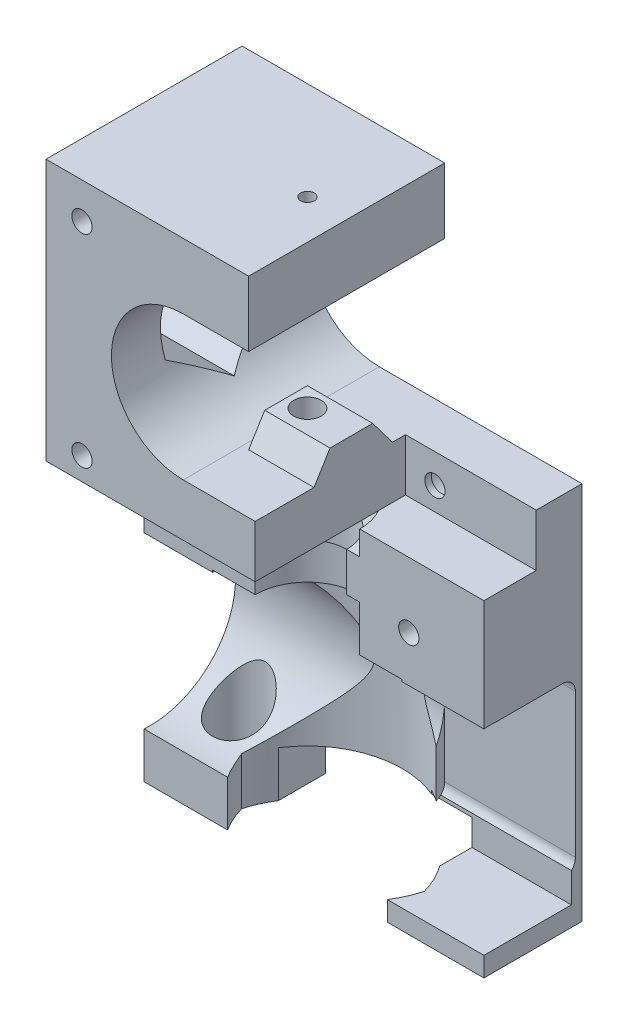
SolidWorks part; units mm, degrees
note: The reader was unsure of these and kept them because the rebuilt part matched: shared geometry of "Croquis16<3>".
ref_plane "Alzado" through (0, 0, 0) normal (0, 0, 1) x (1, 0, 0)
ref_plane "Planta" through (0, 0, 0) normal (0, 1, 0) x (1, 0, 0)
ref_plane "Vista lateral" through (0, 0, 0) normal (1, 0, 0) x (0, 0, -1)
sketch "Croquis2" plane through (0, 0, 0) normal (0, 0, 1) x (1, 0, 0)
  line L0 (0, 0) -> (0, 90)
  line L1 (0, 90) -> (21, 90)
  line L2 (27, 80) -> (31, 80)
  line L3 (21, 58) -> (42, 58)
  line L4 (42, 58) -> (42, 0)
  line L5 (42, 0) -> (0, 0)
  line L6 (21, 80) -> (27, 80)
  line L7 (21, 90) -> (27, 90)
  line L9 (31, 80) -> (31, 90)
  line L10 (31, 90) -> (27, 90)
  circle A0 centre (5.5, 84.5) radius 1.55
  circle A1 centre (5.5, 53.5) radius 1.55
  circle A2 centre (36.5, 53.5) radius 1.55
  arc A3 (21, 80) -> (21, 58) centre (21, 69) ccw
  dimension "D5" = 3.1
  dimension "D6" = 3.1
  dimension "D7" = 3.1
  dimension "D12" = 22
  dimension "D1" = 90
  dimension "D2" = 42
  dimension "D3" = 6
  dimension "D4" = 10
  dimension "D8" = 5.5
  dimension "D9" = 31
  dimension "D10" = 31
  dimension "D11" = 27
  dimension "D13" = 15.5
  dimension "D14" = 15.5
  dimension "D15" = 4
  dimension "D16" = 10
  dimension "D17" = 21
extrude "Saliente-Extruir1" add sketch "Croquis2" along normal blind 30
sketch "Croquis3" plane through (0, 0, 0) normal (0, 0, -1) x (-1, 0, 0)
  circle A0 centre (-5.5, 84.5) radius 1.55 construction
  circle A1 centre (-5.5, 53.5) radius 1.55 construction
  circle A2 centre (-36.5, 53.5) radius 1.55 construction
  circle A3 centre (-5.5, 84.5) radius 1.55
  circle A4 centre (-5.5, 53.5) radius 1.55
  circle A5 centre (-36.5, 53.5) radius 1.55
  circle A6 centre (-36.5, 53.5) radius 2.8
  circle A7 centre (-5.5, 53.5) radius 2.8
  circle A8 centre (-5.5, 84.5) radius 2.8
  dimension "D1" = 5.6
  dimension "D2" = 5.6
  dimension "D3" = 5.6
extrude "Cortar-Extruir1" cut sketch "Croquis3" against normal blind 6
sketch "Croquis5" plane through (0, 0, 30) normal (0, 0, 1) x (1, 0, 0)
  line L0 (32, 58) -> (32, 50)
  line L1 (42, 58) -> (21, 58) construction
  line L2 (32, 50) -> (42, 50)
  line L3 (42, 0) -> (42, 58) construction
  line L4 (42, 0) -> (42, 58)
  line L5 (42, 58) -> (32, 58)
  line M7 (42, 0) -> (42, 58)
  line M8 (42, 58) -> (21, 58)
  circle M15 centre (36.5, 53.5) radius 1.55
  dimension "D1" = 10
  dimension "D2" = 8
extrude "Cortar-Extruir2" cut sketch "Croquis5" against normal blind 23 contours L0 L2 M7 M8 M15
sketch "Croquis6" plane through (0, 0, 30) normal (0, 0, 1) x (1, 0, 0)
  line L0 (42, 50) -> (0, 50)
  line L1 (0, 90) -> (0, 0) construction
  line L2 (0, 50) -> (0, 0)
  line L3 (0, 0) -> (42, 0)
  line L4 (42, 0) -> (42, 50)
extrude "Cortar-Extruir3" cut sketch "Croquis6" against normal blind 15
sketch "Croquis8" plane through (0, 90, 0) normal (0, 1, 0) x (1, 0, 0)
  line L0 (31, 0) -> (0, 0) construction
  line L1 (31, -30) -> (31, 0) construction
  circle A0 centre (25, -15) radius 1.05
  dimension "D1" = 2.1
  dimension "D2" = 15
  dimension "D3" = 6
extrude "Cortar-Extruir4" cut sketch "Croquis8" against normal up to surface (40 mm away) up to face at (16, 50, 22.5)
sketch "Croquis9" plane through (0, 0, 0) normal (-1, 0, 0) x (0, 0, 1)
  line L0 (0, 90) -> (0, 0) construction
  line L1 (15, 60.6795) -> (22.5, 65.0096)
  line L2 (22.5, 65.0096) -> (22.5, 73.6699)
  line L3 (22.5, 73.6699) -> (15, 78)
  line L4 (15, 78) -> (7.5, 73.6699)
  line L5 (7.5, 73.6699) -> (7.5, 65.0096)
  line L6 (7.5, 65.0096) -> (15, 60.6795)
  circle A0 centre (15, 69.3397) radius 7.5 construction
  dimension "D3" = 15
  dimension "D1" = 15
  dimension "D2" = 12
extrude "Cortar-Extruir5" cut sketch "Croquis9" against normal up to surface (11.0405 mm away)
sketch "Croquis13" plane through (0, 0, 15) normal (0, 0, 1) x (1, 0, 0)
  line L0 (26.05, 50) -> (23.95, 50) construction
  line L1 (26.05, 50) -> (23.95, 50) construction
  line L2 (25, 50) -> (17, 50)
  line L3 (32, 50) -> (0, 50) construction
  line L4 (17, 50) -> (17, 46.3)
  line L5 (17, 46.3) -> (19, 46.3)
  line L6 (19, 46.3) -> (19, 40.3)
  line L7 (19, 40.3) -> (17, 40.3)
  line L8 (17, 40.3) -> (17, 33.3)
  line L15 (17, 33.3) -> (10.5, 33.3)
  line L16 (25, 50) -> (25, 7.3)
  line L17 (10.5, 33.3) -> (10.5, 7.3)
  line L18 (10.5, 7.3) -> (25, 7.3)
  dimension "D1" = 8
  dimension "D2" = 3.7
  dimension "D3" = 6
  dimension "D4" = 6
  dimension "D5" = 8
  dimension "D6" = 7
  dimension "D13" = 14.5
  dimension "D14" = 26
revolve "Cortar-Revolución2" cut sketch "Croquis13" angle 360 about L16
sketch "Croquis14" plane through (0, 0, 0) normal (-1, 0, 0) x (0, 0, 1)
  line L0 (15, 50) -> (15, 0) construction
  line L1 (15, 33) -> (15, 7)
  arc A0 (15, 33) -> (15, 7) centre (14.0357, 20) ccw
  point P3 (1, 20)
  point P5 (15, 20)
  dimension "D1" = 17
  dimension "D2" = 26
  dimension "D3" = 14
extrude "Cortar-Extruir7" cut sketch "Croquis14" against normal through all
sketch "Croquis15" plane through (0, 7.3, 0) normal (0, 1, 0) x (1, 0, 0)
  line L1 (11.0353, -11.0964) -> (38.9647, -11.0964) construction
  line L2 (11.0353, -11.0964) -> (38.9647, -11.0964) construction
  arc A1 (38.9647, -11.0964) -> (11.0353, -11.0964) centre (25, -15) ccw construction
  arc A2 (38.9647, -11.0964) -> (11.0353, -11.0964) centre (25, -15) ccw
  arc A3 (38.9647, -11.0964) -> (11.0353, -11.0964) centre (25, -7.1927) cw
extrude "Cortar-Extruir8" cut sketch "Croquis15" against normal through all
sketch "Croquis16" plane through (42, 0, 0) normal (1, 0, 0) x (0, 0, -1)
  line L0 (-15, 33) -> (-3, 33)
  line L1 (-1, 31) -> (-1, 9)
  line L2 (-15, 7) -> (-3, 7)
  arc A0 (-15, 7) -> (-15, 33) centre (-14.0357, 20) ccw construction
  arc A1 (-15, 7) -> (-15, 33) centre (-14.0357, 20) ccw
  arc A2 (-1, 31) -> (-3, 33) centre (-3, 31) ccw
  arc A3 (-1, 9) -> (-3, 7) centre (-3, 9) cw
  point P7 (-1, 33)
  arc M3 (-15, 33) -> (-15, 7) centre (-14.0357, 20) cw
  dimension "D2" = 2
  dimension "D3" = 2
  dimension "D1" = 14
extrude "Cortar-Extruir9" cut sketch "Croquis16" against normal blind 10 contours L1 L0 M3
extrude "Cortar-Extruir10" cut sketch "Croquis16<3>" against normal blind 10 contours L2 L1 M3
sketch "Croquis16<3>" plane through (42, 0, 0) normal (1, 0, 0) x (0, 0, -1) same geometry as "Croquis16"
sketch "Croquis17" plane through (42, 0, 0) normal (1, 0, 0) x (0, 0, -1)
  line L0 (-15, 0) -> (-15, 7) construction
  line L1 (-1.6192, 3.0026) -> (-15, 3.0026)
  line L2 (-1.6192, 3.0026) -> (-1.6192, 7.5532)
  line L4 (-13.0714, 7) -> (-3, 7) construction
  line L5 (-15, 3.0026) -> (-15, 7)
  line L6 (-13.0714, 7) -> (-3, 7)
  arc A1 (-3, 7) -> (-1, 9) centre (-3, 9) ccw construction
  arc A2 (-3, 7) -> (-1.6192, 7.5532) centre (-3, 9) ccw
  dimension "D1" = 13.3808
  dimension "D2" = 3.9974
extrude "Cortar-Extruir11" cut sketch "Croquis17" against normal blind 15
sketch "Croquis18" plane through (42, 0, 0) normal (1, 0, 0) x (0, 0, -1)
  line L11 (-1.6192, 3.0026) -> (-15, 3.0026)
  line L12 (-15, 3.0026) -> (-15, 0)
  line L13 (-15, 0) -> (0, 0)
  line L14 (0, 0) -> (0, 58)
  line L15 (0, 58) -> (-7, 58)
  line L16 (-7, 58) -> (-7, 50)
  line L17 (-7, 50) -> (-15, 50)
  line L18 (-15, 50) -> (-15, 33)
  line L19 (-13.0714, 33) -> (-3, 33)
  line L20 (-1, 31) -> (-1, 9)
  line L21 (-1.6192, 7.5532) -> (-1.6192, 3.0026)
  line L22 (-1.6192, 3.0026) -> (-15, 3.0026)
  line L23 (-15, 3.0026) -> (-15, 0)
  line L24 (-15, 0) -> (0, 0)
  line L25 (0, 0) -> (0, 58)
  line L26 (0, 58) -> (-7, 58)
  line L27 (-7, 58) -> (-7, 50)
  line L28 (-7, 50) -> (-15, 50)
  line L29 (-15, 50) -> (-15, 33)
  line L30 (-13.0714, 33) -> (-3, 33)
  line L31 (-1, 31) -> (-1, 9)
  line L32 (-1.6192, 7.5532) -> (-1.6192, 3.0026)
  arc A3 (-13.0714, 33) -> (-15, 33) centre (-14.0357, 20) ccw
  arc A4 (-1, 31) -> (-3, 33) centre (-3, 31) ccw
  arc A5 (-1.6192, 7.5532) -> (-1, 9) centre (-3, 9) ccw
  arc A6 (-13.0714, 33) -> (-15, 33) centre (-14.0357, 20) ccw
  arc A7 (-1, 31) -> (-3, 33) centre (-3, 31) ccw
  arc A8 (-1.6192, 7.5532) -> (-1, 9) centre (-3, 9) ccw
  dimension "D1" = 0
extrude "Saliente-Extruir2" add sketch "Croquis18" along normal blind 10
sketch "Croquis19" plane through (0, 0, 15) normal (0, 0, 1) x (1, 0, 0)
  line L0 (52, 50) -> (52, 33) construction
  line L1 (0, 50) -> (0, 33) construction
  circle A0 centre (40.5, 40) radius 1.55
  circle A1 centre (12.5, 40) radius 1.55
  dimension "D1" = 3.1
  dimension "D2" = 3.1
  dimension "D3" = 11.5
  dimension "D4" = 12.5
  dimension "D5" = 10
extrude "Cortar-Extruir12" cut sketch "Croquis19" against normal through all
sketch "Croquis21" plane through (0, 0, 0) normal (0, -1, 0) x (1, 0, 0)
  circle A0 centre (6.5, 7) radius 4.05
  dimension "D1" = 8.1
  dimension "D2" = 6.5
  dimension "D3" = 7
extrude "Cortar-Extruir13" cut sketch "Croquis21" against normal blind 44
sketch "Croquis22" plane through (0, 0, 0) normal (-1, 0, 0) x (0, 0, 1)
  circle A0 centre (7.4528, 42.2128) radius 2
  dimension "D1" = 4
extrude "Cortar-Extruir14" cut sketch "Croquis22" against normal up to surface (3.2772 mm away)
sketch "Croquis24" plane through (32, 0, 0) normal (1, 0, 0) x (0, 0, -1)
  line L0 (-15, 58) -> (-21, 58)
  line L2 (-7, 58) -> (-30, 58) construction
  line L3 (-15, 58) -> (-9, 58)
  line L4 (-21, 58) -> (-18.5418, 62)
  line L5 (-18.5418, 62) -> (-12.0124, 62)
  line L6 (-13.95, 58) -> (-16.05, 58) construction
  line L7 (-13.95, 58) -> (-16.05, 58)
  line L8 (-12.0124, 62) -> (-9, 58)
  dimension "D1" = 6
  dimension "D2" = 6
  dimension "D3" = 6.5294
  dimension "D4" = 4
  dimension "D5" = 5.0074
extrude "Saliente-Extruir3" add sketch "Croquis24" against normal blind 10
sketch "Croquis25" plane through (0, 50, 0) normal (0, -1, 0) x (1, 0, 0)
  circle A1 centre (25, 15) radius 1.05 construction
  circle A2 centre (25, 15) radius 1.05 construction
  circle A3 centre (25, 15) radius 2.1
  dimension "D2" = 4.2
extrude "Cortar-Extruir16" cut sketch "Croquis25" against normal up to surface (12 mm away) up to face at (27, 62, 15.2771)
sketch "Croquis26" plane through (0, 0, 15) normal (0, 0, 1) x (1, 0, 0)
  line L0 (12.7813, 0) -> (12.7813, 7)
  line L1 (12.7813, 7) -> (12.7813, 0) construction
  line L2 (12.7813, 7) -> (36.7813, 7)
  line L3 (36.7813, 7) -> (36.7813, 0)
  line L4 (11.0353, 0) -> (38.9647, 0) construction
  line L5 (36.7813, 0) -> (12.7813, 0)
  dimension "D1" = 24
  dimension "D2" = 7
extrude "Cortar-Extruir17" cut sketch "Croquis26" against normal through all
